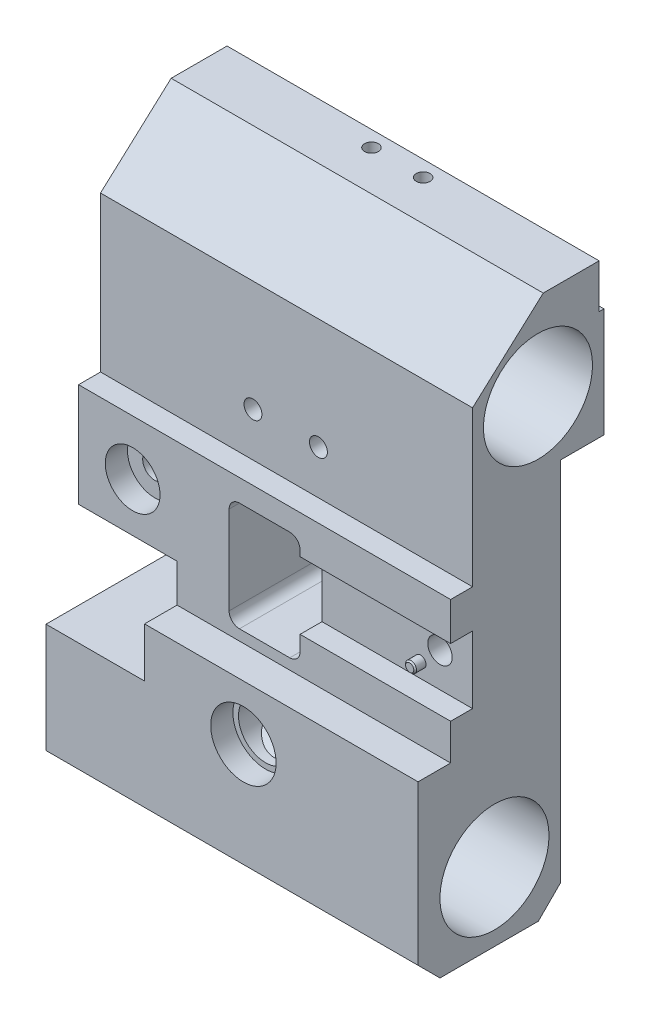
SolidWorks part; units mm, degrees
material "1060 Alloy"
ref_plane "Front Plane" through (0, 0, 0) normal (0, 0, 1) x (1, 0, 0)
ref_plane "Top Plane" through (0, 0, 0) normal (0, 1, 0) x (1, 0, 0)
ref_plane "Right Plane" through (0, 0, 0) normal (1, 0, 0) x (0, 0, -1)
sketch "Sketch1" plane through (0, 0, 0) normal (1, 0, 0) x (0, 0, -1)
  line L0 (14.15, 137.2) -> (30.37, 137.2)
  line L1 (30.37, 137.2) -> (30.37, 124.41)
  line L2 (30.37, 124.41) -> (31.79, 124.41)
  line L3 (31.79, 124.41) -> (31.79, 92.72)
  line L4 (31.79, 92.72) -> (19.1, 92.72)
  line L5 (19.1, 92.72) -> (19.1, -13.636)
  line L6 (19.1, -13.636) -> (12.736, -20)
  line L7 (12.736, -20) -> (-15.816, -20)
  line L8 (-15.816, -20) -> (-22.18, -13.636)
  line L9 (-22.18, -13.636) -> (-22.18, 32.5)
  line L10 (-22.18, 32.5) -> (-12.73, 32.5)
  line L11 (-12.73, 32.5) -> (-12.73, 73.61)
  line L12 (-12.73, 73.61) -> (-6.36, 73.61)
  line L13 (-6.36, 73.61) -> (-6.36, 118.61)
  line L14 (-6.36, 118.61) -> (14.15, 137.2)
  line L15 (-22.18, 32.5) -> (-22.18, 137.2) construction
  line L16 (-22.18, 137.2) -> (14.15, 137.2) construction
  line L17 (30.37, 137.2) -> (31.79, 137.2) construction
  line L18 (31.79, 137.2) -> (31.79, 124.41) construction
  line L19 (31.79, 92.72) -> (31.79, -20) construction
  line L20 (31.79, -20) -> (12.736, -20) construction
  line L21 (-22.18, -13.636) -> (-22.18, -20) construction
  line L22 (-22.18, -20) -> (-15.816, -20) construction
  line L23 (-22.18, 0) -> (31.79, 0) construction
  line L24 (0, -20) -> (0, 17.0401) construction
  line L25 (-22.18, -13.636) -> (19.1, -13.636) construction
  line L26 (0, -15.83) -> (46.0148, -15.83) construction
  line L27 (15.83, 0) -> (15.83, 26.825) construction
  line L28 (0, 15.83) -> (31.79, 15.83) construction
  line L29 (12.625, 111.985) -> (46.8932, 111.985) construction
  line L30 (12.625, 127.815) -> (56.5516, 127.815) construction
  line L31 (12.625, 96.155) -> (52.1782, 96.155) construction
  line L32 (30.37, 124.41) -> (30.37, 97.4751) construction
  line L33 (-15.83, 0) -> (-15.83, 21.2691) construction
  circle A0 centre (0, 0) radius 15.83
  circle A1 centre (12.625, 111.985) radius 15.83
  dimension "D19" = 111.985
  dimension "D14" = 31.66
  dimension "D1" = 41.28
  dimension "D2" = 38.15
  dimension "D3" = 157.2
  dimension "D4" = 44.48
  dimension "D5" = 1.42
  dimension "D6" = 31.69
  dimension "D7" = 25.46
  dimension "D8" = 31.83
  dimension "D9" = 52.5
  dimension "D10" = 93.61
  dimension "D11" = 9
  dimension "D12" = 12.625
  dimension "D13" = 16.22
  dimension "D15" = 45
  dimension "D16" = 3.27
  dimension "D17" = 6.35
  dimension "D18" = 4.17
extrude "Boss-Extrude1" add sketch "Sketch1" along normal blind 54 and the other way blind 54
sketch "Sketch2" plane through (0, 0, -19.1) normal (0, 0, -1) x (-1, 0, 0)
  line L0 (54, -13.636) -> (54, 92.72) construction
  line L1 (-7.3, 67.2) -> (7.3, 67.2)
  line L2 (-10.3, 64.2) -> (-10.3, 38.6)
  line L3 (-7.3, 35.6) -> (7.3, 35.6)
  line L4 (10.3, 64.2) -> (10.3, 38.6)
  line L5 (54, 43.53) -> (25.4, 43.53)
  line L6 (54, 43.53) -> (54, 18.13)
  line L7 (54, 18.13) -> (25.4, 18.13)
  line L8 (25.4, 43.53) -> (25.4, 18.13)
  line L9 (-9.25, 86.37) -> (9.75, 86.37) construction
  line L10 (-10.3, 64.2) -> (-10.3, 67.2) construction
  line L11 (-10.3, 67.2) -> (-7.3, 67.2) construction
  line L12 (7.3, 67.2) -> (10.3, 67.2) construction
  line L13 (10.3, 67.2) -> (10.3, 64.2) construction
  line L14 (10.3, 38.6) -> (10.3, 35.6) construction
  line L15 (10.3, 35.6) -> (7.3, 35.6) construction
  line L16 (-7.3, 35.6) -> (-10.3, 35.6) construction
  line L17 (-10.3, 35.6) -> (-10.3, 38.6) construction
  line L18 (-54, -13.636) -> (-54, 92.72) construction
  line L19 (54, -20) -> (-54, -20) construction
  line L21 (54, 137.2) -> (-54, 137.2) construction
  line L22 (-3.3, 16.595) -> (-3.3, 92.72) construction
  line L25 (54, 92.72) -> (-54, 92.72) construction
  line L26 (9.75, 86.37) -> (9.75, 92.72) construction
  line L27 (-9.25, 86.37) -> (-9.25, 92.72) construction
  line L28 (38.3, 57.72) -> (38.3, 92.72) construction
  line L29 (-44.55, 52.92) -> (-44.55, 92.72) construction
  circle A0 centre (-3.3, 16.595) radius 7.875
  circle A1 centre (-44.55, 52.92) radius 5.5 construction
  circle A2 centre (38.3, 57.72) radius 5.55 construction
  circle A3 centre (-9.25, 86.37) radius 2.6
  circle A4 centre (9.75, 86.37) radius 2.6
  circle A5 centre (-3.3, 16.595) radius 9.42 construction
  circle A6 centre (-9.25, 86.37) radius 4.425 construction
  circle A7 centre (9.75, 86.37) radius 4.425 construction
  circle A8 centre (38.3, 57.72) radius 3.525
  circle A9 centre (-44.55, 52.92) radius 3.55
  arc A10 (-7.3, 35.6) -> (-10.3, 38.6) centre (-7.3, 38.6) cw
  arc A11 (7.3, 35.6) -> (10.3, 38.6) centre (7.3, 38.6) ccw
  arc A12 (7.3, 67.2) -> (10.3, 64.2) centre (7.3, 64.2) cw
  arc A13 (-7.3, 67.2) -> (-10.3, 64.2) centre (-7.3, 64.2) ccw
  dimension "D1" = 3
  dimension "D17" = 18.84
  dimension "D18" = 15.75
  dimension "D20" = 8.85
  dimension "D21" = 5.2
  dimension "D22" = 7.05
  dimension "D23" = 11.1
  dimension "D24" = 7.1
  dimension "D25" = 11
  dimension "D2" = 43.7
  dimension "D3" = 43.7
  dimension "D4" = 55.6
  dimension "D5" = 70
  dimension "D6" = 38.13
  dimension "D7" = 25.4
  dimension "D8" = 28.6
  dimension "D9" = 15.7
  dimension "D10" = 44.25
  dimension "D11" = 63.25
  dimension "D12" = 9.45
  dimension "D13" = 50.7
  dimension "D14" = 35
  dimension "D15" = 6.35
  dimension "D16" = 39.8
  dimension "D19" = 76.125
extrude "Cut-Extrude1" cut sketch "Sketch2" against normal through all
sketch "Sketch3" plane through (0, 0, 12.73) normal (0, 0, 1) x (1, 0, 0)
  line L0 (54, 73.61) -> (54, 32.5) construction
  line L1 (54, 43) -> (10.3, 43)
  line L2 (54, 43) -> (54, 62.52)
  line L3 (54, 62.52) -> (10.3, 62.52)
  line L4 (10.3, 43) -> (10.3, 62.52)
  line L5 (10.3, 38.6) -> (10.3, 64.2) construction
  line L6 (-25.4, 32.5) -> (54, 32.5) construction
  dimension "D1" = 10.5
  dimension "D2" = 19.52
extrude "Cut-Extrude2" cut sketch "Sketch3" against normal blind 6.36
sketch "Sketch4" plane through (0, 0, 6.37) normal (0, 0, 1) x (1, 0, 0)
  line L0 (40.5, 47.335) -> (54, 47.335) construction
  line L2 (54, 43) -> (54, 62.52) construction
  line L3 (38.915, 48.92) -> (38.915, 62.52) construction
  line L4 (54, 62.52) -> (10.3, 62.52) construction
  circle A0 centre (38.915, 47.335) radius 1.585
  dimension "D1" = 3.17
  dimension "D2" = 13.5
  dimension "D3" = 13.6
extrude "Boss-Extrude2" add sketch "Sketch4" along normal blind 3.15
sketch "Sketch10" plane through (0, 0, -19.1) normal (0, 0, -1) x (-1, 0, 0)
  circle A1 centre (-38.915, 47.335) radius 1.585
  circle A2 centre (-38.915, 47.335) radius 1.585
  dimension "D1" = 0
extrude "Cut-Extrude6" cut sketch "Sketch10" against normal blind 20
sketch "Sketch11" plane through (0, 0, -19.1) normal (0, 0, -1) x (-1, 0, 0)
  circle A0 centre (38.3, 57.72) radius 5.5
  circle A1 centre (-44.55, 52.92) radius 5.42
  circle A2 centre (-9.25, 86.37) radius 4.55
  circle A3 centre (9.75, 86.37) radius 4.55
  circle M11 centre (38.3, 57.72) radius 3.525
  circle M12 centre (9.75, 86.37) radius 2.6
  circle M13 centre (-9.25, 86.37) radius 2.6
  dimension "D1" = 10.84
  dimension "D2" = 11
  dimension "D3" = 9.1
extrude "Cut-Extrude7" cut sketch "Sketch11" against normal blind 6.56 contours A0 M11 | A1 region at (-32.9556, 57.72, -19.1)
chamfer "Chamfer1" distance 0.4 angle 45 1 edges at (40.5, 47.335, 9.52)
sketch "Sketch5" plane through (0, 0, 12.73) normal (0, 0, 1) x (1, 0, 0)
  circle A0 centre (-38.3, 57.72) radius 7.945
  dimension "D1" = 15.89
extrude "Cut-Extrude3" cut sketch "Sketch5" against normal blind 6.44
sketch "Sketch6" plane through (0, 0, 22.18) normal (0, 0, 1) x (1, 0, 0)
  circle A0 centre (3.3, 16.595) radius 9.495
  dimension "D1" = 18.99
extrude "Cut-Extrude4" cut sketch "Sketch6" against normal blind 6.44
sketch "Sketch7" plane through (0, 0, -19.1) normal (0, 0, -1) x (-1, 0, 0)
  line L0 (25.4, 43.53) -> (25.4, 18.13) construction
  line L1 (25.4, 34.07) -> (16.63, 34.07)
  line L2 (25.4, 34.07) -> (25.4, -0.89)
  line L3 (25.4, -0.89) -> (16.63, -0.89)
  line L4 (16.63, 34.07) -> (16.63, -0.89)
  line L5 (54, 92.72) -> (-54, 92.72) construction
  dimension "D1" = 8.77
  dimension "D2" = 34.96
  dimension "D3" = 58.65
extrude "Boss-Extrude3" add sketch "Sketch7" along normal blind 3.1
sketch "Sketch8" plane through (0, 0, -22.2) normal (0, 0, -1) x (-1, 0, 0)
  line L0 (21.4, 3.82) -> (21.4, 92.72) construction
  line L1 (54, 92.72) -> (-54, 92.72) construction
  line L2 (16.63, -0.89) -> (25.4, -0.89) construction
  line L5 (25.4, -0.89) -> (25.4, 34.07) construction
  circle A0 centre (21.4, 29.135) radius 2
  circle A1 centre (21.4, 3.82) radius 2
  dimension "D2" = 4
  dimension "D1" = 4
  dimension "D3" = 4.71
  dimension "D4" = 30.025
extrude "Cut-Extrude5" cut sketch "Sketch8" against normal blind 15
extrude "Cut-Extrude8" cut sketch "Sketch11<3>" against normal blind 5.45 contours A2 M13 | A3 M12 region at (13.6713, 86.37, -19.1) region at (-5.3287, 86.37, -19.1)
sketch "Sketch11<3>" plane through (0, 0, -19.1) normal (0, 0, -1) x (-1, 0, 0) same geometry as "Sketch11"
sketch "Sketch12" plane through (0, 0, -19.1) normal (0, 0, -1) x (-1, 0, 0)
  circle A0 centre (-3.3, 16.595) radius 9.475
  dimension "D1" = 18.95
extrude "Cut-Extrude9" cut sketch "Sketch12" against normal blind 5.15
sketch "Sketch13" plane through (0, 0, -19.1) normal (0, 0, -1) x (-1, 0, 0)
  line L0 (-17.6348, 41.72) -> (20.3, 41.72) construction
  line L1 (-13.5, 41.72) -> (-13.5, 73.72) construction
  line L2 (13.2, 41.72) -> (13.2, 73.72) construction
  line L3 (-13.5, 73.72) -> (13.2, 73.72) construction
  line L4 (54, 92.72) -> (-54, 92.72) construction
  line L5 (-54, -13.636) -> (-54, 92.72) construction
  circle A0 centre (-13.5, 73.72) radius 2
  circle A1 centre (13.2, 73.72) radius 2
  circle A2 centre (-13.5, 41.72) radius 2
  circle A3 centre (13.2, 41.72) radius 2
  circle A4 centre (20.3, 41.72) radius 2
  circle A5 centre (-21, 41.92) radius 2
  circle A6 centre (21.4, 29.135) radius 2 construction
  dimension "D3" = 40.5
  dimension "D1" = 51
  dimension "D2" = 19
  dimension "D4" = 67.2
  dimension "D5" = 33
  dimension "D6" = 0.2
  dimension "D7" = 74.3
sketch "Sketch14" plane through (0, 0, -30.37) normal (0, 0, -1) x (-1, 0, 0)
  line L0 (-0.2, 130.91) -> (-0.2, 124.41) construction
  line L1 (54, 124.41) -> (-54, 124.41) construction
  line L2 (-0.2, 130.91) -> (-54, 130.91) construction
  line L3 (-54, 124.41) -> (-54, 137.2) construction
  circle A0 centre (-0.2, 130.91) radius 2
  circle A1 centre (13.2, 73.72) radius 2 construction
  dimension "D1" = 53.8
  dimension "D2" = 6.5
extrude "Cut-Extrude10" cut sketch "Sketch13" against normal blind 10
extrude "Cut-Extrude11" cut sketch "Sketch14" against normal blind 10
ref_axis "Axis1" through (-54, 111.985, -12.625) along (1, 0, 0)
ref_axis "Axis2" through (-54, 0, 0) along (1, 0, 0)
sketch "Sketch15" plane through (0, 137.2, 0) normal (0, 1, 0) x (-1, 0, 0)
  line L0 (0, -30.37) -> (0, -14.15) construction
  line L1 (54, -30.37) -> (-54, -30.37) construction
  line L2 (54, -14.15) -> (-54, -14.15) construction
  line L3 (-54, -30.37) -> (-54, -14.15) construction
  line L4 (54, -30.37) -> (54, -14.15) construction
  line L5 (12.7, -30.37) -> (12.7, -14.15) construction
  line L6 (-12.7, -30.37) -> (-12.7, -14.15) construction
  line L7 (54, -19.1) -> (-54, -19.1) construction
  line L8 (54, -19.1) -> (-54, -19.1) construction
  line L9 (54, -22.15) -> (-54, -22.15) construction
  line L10 (54, -12.625) -> (-54, -12.625) construction
  line L11 (54, -28.455) -> (54, 3.205) construction
  line L12 (54, -31.79) -> (-54, -31.79) construction
  line L13 (54, -31.79) -> (-54, -31.79) construction
  line L14 (7.5, -25.79) -> (-7.5, -25.79) construction
  line L15 (-54, -28.455) -> (54, -28.455) construction
  circle A0 centre (7.5, -25.79) radius 2
  circle A1 centre (-7.5, -25.79) radius 2
  dimension "D3" = 4
  dimension "D1" = 25.4
  dimension "D2" = 19.05
  dimension "D4" = 15
  dimension "D5" = 6
extrude "Cut-Extrude12" cut sketch "Sketch15" against normal up to surface (44.48 mm away) up to face at (0, 92.72, -25.445)
sketch "Sketch16" plane through (-25.4, 0, 0) normal (-1, 0, 0) x (0, 0, 1)
  line L0 (-8.6318, 32.3686) -> (7.5827, 28.5816) construction
  circle A0 centre (7.5827, 28.5816) radius 2
  circle A1 centre (-8.6318, 32.3686) radius 2
  dimension "D1" = 4
extrude "Cut-Extrude13" cut sketch "Sketch16" against normal blind 25
sketch "Sketch17" plane through (0, 0, -19.1) normal (0, 0, -1) x (-1, 0, 0)
  line L0 (-25.3804, 28.2306) -> (-44.7373, 28.2306) construction
  circle A0 centre (-44.7373, 28.2306) radius 2
  circle A1 centre (-25.3804, 28.2306) radius 2
  dimension "D1" = 4
extrude "Cut-Extrude14" [suppressed] cut sketch "Sketch17" against normal blind 25
sketch "Sketch18" plane through (0, 0, -19.1) normal (0, 0, -1) x (-1, 0, 0)
  line L0 (7.5, -7.027) -> (-7.5, -7.027) construction
  line L5 (-31.422, -11.527) -> (52.578, -11.527) construction
  line L6 (52.578, -2.527) -> (3.578, -2.527) construction
  line L7 (7.5, -7.027) -> (12.725, -7.027) construction
  line L8 (-7.5, -7.027) -> (-12.725, -7.027) construction
  line L9 (12.725, -15.875) -> (12.725, 15.875) construction
  line L10 (-12.725, -15.875) -> (-12.725, 15.875) construction
  line L11 (-7.5, -9.027) -> (-13.1525, -9.027) construction
  line L12 (-18.422, -6.527) -> (-2.2002, -6.527) construction
  line L13 (-7.5, -9.027) -> (-7.5, -7.027) construction
  circle A0 centre (7.5, -7.027) radius 2
  circle A1 centre (-7.5, -7.027) radius 2 construction
  circle A2 centre (-7.5, -9.027) radius 2
  dimension "D1" = 4
  dimension "D2" = 15
extrude "Cut-Extrude15" cut sketch "Sketch18" against normal up to next
sketch "Sketch19" plane through (0, 0, -19.1) normal (0, 0, -1) x (-1, 0, 0)
  circle A0 centre (-26.922, 67.473) radius 2.3 construction
  circle A1 centre (-26.922, 67.473) radius 2.3
  circle A2 centre (-26.922, 26.298) radius 2.3 construction
  circle A3 centre (-26.922, 67.473) radius 2.3
  circle A4 centre (-26.922, 26.298) radius 2.3
extrude "Cut-Extrude16" cut sketch "Sketch19" against normal blind 20 contours A1 | A4 region at (26.922, 67.473, -19.1) region at (26.922, 26.298, -19.1)
